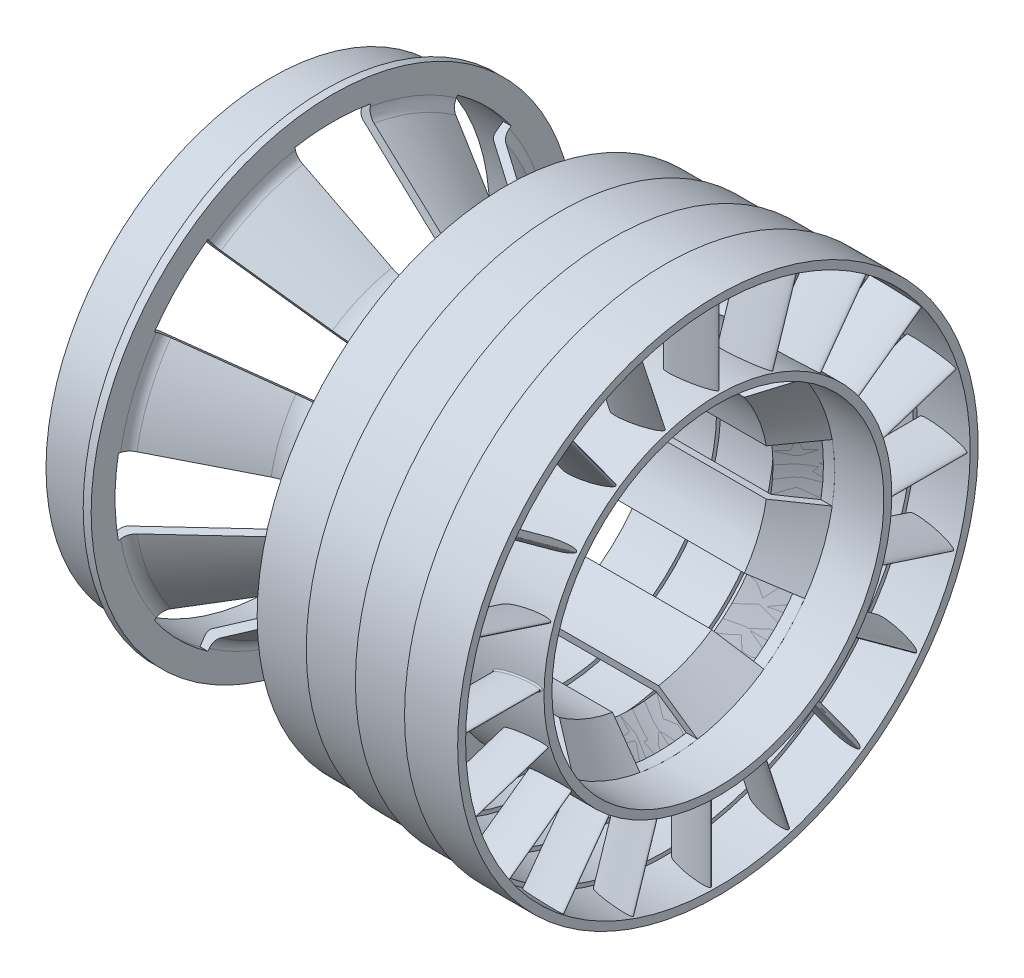
SolidWorks part; units mm, degrees
ref_plane "Front Plane" through (0, 0, 0) normal (0, 0, 1) x (1, 0, 0)
ref_plane "Top Plane" through (0, 0, 0) normal (0, 1, 0) x (1, 0, 0)
ref_plane "Right Plane" through (0, 0, 0) normal (1, 0, 0) x (0, 0, -1)
sketch "Sketch1" plane through (0, 0, 0) normal (0, 0, 1) x (1, 0, 0)
  line L0 (-65, 0) -> (65, 0) construction
  line L1 (-37.1569, 90.5) -> (-45.5558, 90.5)
  line L2 (14.4442, 95) -> (34.4442, 95)
  line L3 (14.4442, 96.5) -> (14.4442, 98)
  line L4 (14.4442, 98) -> (34.4442, 98)
  line L5 (34.4442, 95) -> (34.4442, 98)
  line L6 (14.4442, 96.5) -> (-5.5558, 96.5)
  line L7 (14.4442, 95) -> (14.4442, 93.5)
  line L8 (14.4442, 93.5) -> (-5.5558, 93.5)
  line L9 (-5.5558, 96.5) -> (-5.5558, 95)
  line L10 (-5.5558, 95) -> (-25.5558, 95)
  line L11 (-5.5558, 93.5) -> (-5.5558, 92)
  line L12 (-5.5558, 92) -> (-25.5558, 92)
  line L13 (-25.5558, 95) -> (-25.5558, 93.5)
  line L14 (-25.5558, 93.5) -> (-45.5558, 93.5)
  line L15 (-25.5558, 92) -> (-25.5558, 90.5)
  line L16 (-25.5558, 90.5) -> (-34.1569, 90.5)
  line L17 (-45.5558, 93.5) -> (-45.5558, 90.5)
  line L23 (-37.1569, 90.5) -> (-37.1569, 62.5)
  line L25 (-34.1569, 90.5) -> (-34.1569, 62.5)
  line L26 (-45.5558, 62.5) -> (-37.1569, 62.5)
  line L27 (-45.5558, 62.5) -> (-45.5558, 59.5)
  line L28 (-45.5558, 59.5) -> (-25.5558, 59.5)
  line L29 (-25.5558, 61) -> (-25.5558, 59.5)
  line L30 (-25.5558, 61) -> (-5.5558, 61)
  line L31 (-25.5558, 62.5) -> (-25.5558, 64)
  line L32 (-25.5558, 64) -> (-5.5558, 64)
  line L33 (-5.5558, 61) -> (-5.5558, 62.5)
  line L34 (-5.5558, 62.5) -> (11.7016, 62.5)
  line L35 (-5.5558, 64) -> (-5.5558, 65.5)
  line L36 (-5.5558, 65.5) -> (34.4442, 65.5)
  line L37 (34.4442, 62.5) -> (34.4442, 65.5)
  line L38 (-34.1569, 62.5) -> (-25.5558, 62.5)
  line L39 (15.9442, 62.5) -> (3.4442, 50)
  line L40 (15.9442, 62.5) -> (34.4442, 62.5)
  line L41 (2.2016, 53) -> (11.7016, 62.5)
  line L42 (-78.5558, 56.0877) -> (-110.5558, 78.5591)
  line L43 (3.4442, 50) -> (-69.7342, 50)
  line L45 (2.2016, 53) -> (-68.7861, 53)
  line L47 (-110.5558, 78.5591) -> (-110.5558, 91)
  line L48 (-110.5558, 91) -> (-113.5558, 91)
  line L49 (-113.5558, 91) -> (-113.5558, 85)
  line L50 (-113.5558, 85) -> (-133.5558, 85)
  line L51 (-133.5558, 85) -> (-133.5558, 82)
  line L52 (-133.5558, 82) -> (-113.5558, 82)
  line L53 (-113.5558, 82) -> (-113.5558, 77)
  line L54 (-113.5558, 77) -> (-79.5039, 53.0877)
  line L55 (3.4442, 50) -> (43.4454, 50) construction
  arc A0 (-79.5039, 53.0877) -> (-69.7342, 50) centre (-69.7342, 67) ccw
  arc A1 (-78.5558, 56.0877) -> (-68.7861, 53) centre (-68.7861, 70) ccw
  point P3 (0, 0)
  point P57 (14.4442, 65.5)
  dimension "D23" = 17
  dimension "D1" = 3
  dimension "D2" = 20
  dimension "D3" = 34
  dimension "D4" = 1.5
  dimension "D5" = 3
  dimension "D6" = 40
  dimension "D7" = 3
  dimension "D8" = 3
  dimension "D9" = 3
  dimension "D10" = 9
  dimension "D11" = 23
  dimension "D12" = 82
  dimension "D13" = 1.5
  dimension "D14" = 1.5
  dimension "D15" = 59.5
  dimension "D16" = 3
  dimension "D19" = 1.5
  dimension "D20" = 45
  dimension "D21" = 50
  dimension "D22" = 3
  dimension "D24" = 55
  dimension "D25" = 168
  dimension "D26" = 5
  dimension "D27" = 1.5
  dimension "D28" = 1.5
revolve "Revolve1" add sketch "Sketch1" angle 360 about L0
fillet "Fillet1" radius 5 1 edges at (-110.5558, 0, 78.5591)
fillet "Fillet2" radius 3 1 edges at (-113.5558, 0, 77)
sketch "Sketch2" plane through (0, 0, 0) normal (0, 0, 1) x (1, 0, 0)
  line L0 (-183.2935, 0) -> (153.0908, 0) construction
  line L1 (-139.7817, 0) -> (-139.7817, 81.9956)
  line L2 (-139.7817, 81.9956) -> (-45.5558, 81.9956)
  line L3 (-45.5558, 90.5) -> (-45.5558, -90.5) construction
  line L4 (-45.5558, 81.9956) -> (-45.5558, 53)
  line L5 (-45.5558, 59.5) -> (-45.5558, -59.5) construction
  line L6 (-45.5558, 53) -> (2.2016, 53)
  line L7 (2.2016, 53) -> (2.2016, -53) construction
  line L8 (2.2016, 53) -> (11.7016, 62.4902)
  line L9 (11.7016, 62.5) -> (11.7016, -62.5) construction
  line L10 (11.7016, 62.4902) -> (54.3541, 62.4902)
  line L11 (54.3541, 62.4902) -> (54.3541, 0)
  line L12 (54.3541, 0) -> (-139.7817, 0)
  point P5 (-139.8317, 81.8794)
  point P20 (-139.7817, 81.9939)
  point P21 (-45.5558, 53)
  point P22 (11.7016, 62.4902)
revolve "Cut-Revolve2" cut sketch "Sketch2" angle 20 mid plane about L0
pattern_circular "CirPattern1" count 8 over 360 about axis through (-112.2798, 0, 0) along (-1, 0, 0) of "Cut-Revolve2"
sketch "Sketch8" plane through (-37.1569, 0, 0) normal (-1, 0, 0) x (0, 0, 1)
  circle A0 centre (0, 75) radius 5
  circle A1 centre (0, 75) radius 6.5
  dimension "D1" = 10
  dimension "D3" = 75
  dimension "D2" = 1.5
extrude "Boss-Extrude2" add sketch "Sketch8" along normal blind 5
sketch "Sketch4" plane through (0, 0, 0) normal (1, 0, 0) x (0, 0, -1)
  circle A0 centre (0, 75) radius 5
  circle A1 centre (0, 75) radius 6.5
  dimension "D1" = 10
  dimension "D2" = 75
  dimension "D3" = 1.5
sketch "Sketch7" plane through (-37.1569, 0, 0) normal (-1, 0, 0) x (0, 0, 1)
  circle A3 centre (0, 75) radius 5
  dimension "D1" = 10
extrude "Cut-Extrude6" cut sketch "Sketch7" against normal through all
pattern_circular "CirPattern6" count 10 over 360 about axis through (-45.5558, 0, 0) along (-1, 0, 0) of "Cut-Extrude6", "Boss-Extrude2"
sketch "Sketch9" plane through (0, 0, 0) normal (0, 0, 1) x (1, 0, 0)
  line L0 (-153.7104, 0) -> (108.1191, 0) construction
  line L3 (24.4442, 0) -> (33.3075, 1.5628) construction
  ellipse E0 centre (24.4442, 0) end of major axis (15.581, -1.5628) minor radius 1.5
  dimension "D1" = 3
  dimension "D2" = 18
  dimension "D3" = 10
extrude "Boss-Extrude3" add sketch "Sketch9" along normal up to surface (29.9871 mm away) from offset 65 up to face at (34.4442, 0, 95)
fillet "Fillet4" radius 0.5 2 edges at (17.4936, -0.2451, 94.9997) (19.6219, 0.4517, 65.4984)
pattern_circular "CirPattern7" count 20 over 360 about axis through (-65, 0, 0) along (-1, 0, 0) of "Boss-Extrude3"
equation "\"37.5.00mm\"=38"
